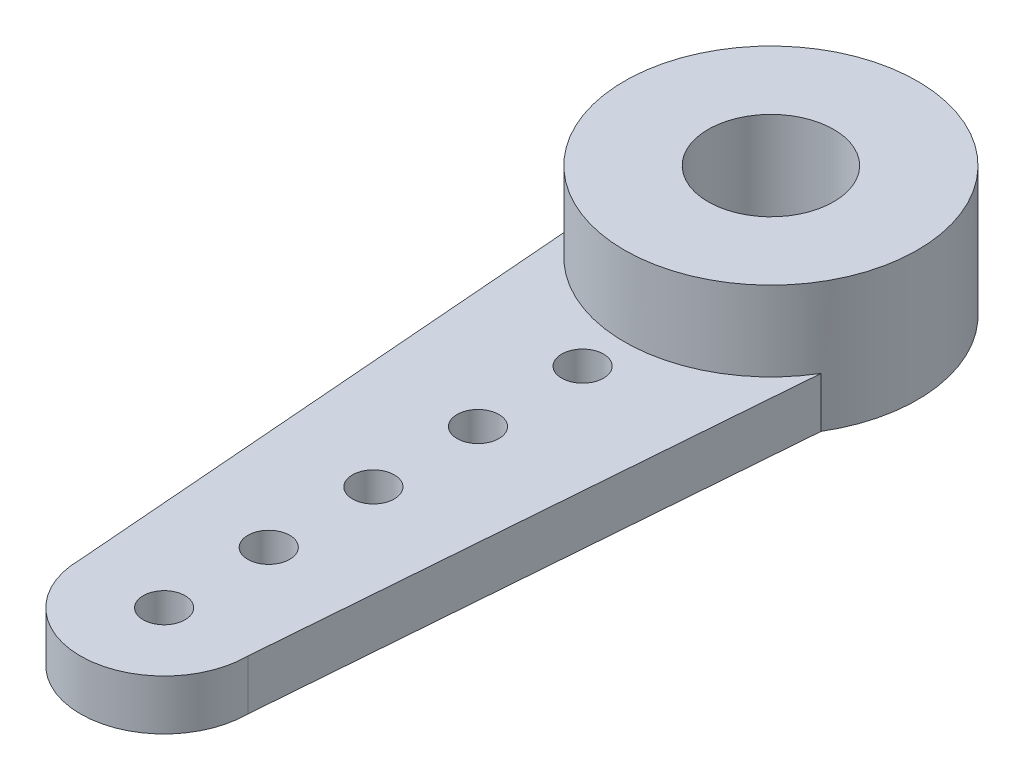
SolidWorks part; units mm, degrees
ref_plane "Front" through (0, 0, 0) normal (0, 0, 1) x (1, 0, 0)
ref_plane "Top" through (0, 0, 0) normal (0, 1, 0) x (1, 0, 0)
ref_plane "Right" through (0, 0, 0) normal (1, 0, 0) x (0, 0, -1)
sketch "草图1" plane through (0, 0, 0) normal (0, 1, 0) x (1, 0, 0)
  line L0 (-81.081, 0) -> (81.6093, 0) construction
  line L1 (0, 48.1996) -> (0, -46.0868) construction
  circle A0 centre (0, 0) radius 3.5
  dimension "D1" = 7
extrude "凸台-拉伸1" add sketch "草图1" along normal blind 3.1
sketch "草图2" plane through (0, 0, 0) normal (0, 1, 0) x (1, 0, 0)
  line L14 (-3, -1.8028) -> (-2, -14.5)
  line L15 (3, -1.8028) -> (2, -14.5)
  arc A1 (2, -14.5) -> (-2, -14.5) centre (0, -14.5) cw
  arc A3 (-3, -1.8028) -> (3, -1.8028) centre (0, 0) ccw
  dimension "D2" = 2
  dimension "D1" = 6
extrude "凸台-拉伸2" add sketch "草图2" along normal blind 1.2
sketch "草图3" plane through (0, 3.1, 0) normal (0, 1, 0) x (1, 0, 0)
  circle A0 centre (0, 0) radius 1.5
  dimension "D1" = 3
extrude "切除-拉伸1" cut sketch "草图3" against normal blind 3
sketch "草图4" plane through (0, 1.2, 0) normal (0, 1, 0) x (1, 0, 0)
  circle A0 centre (0, -14.5) radius 0.5
  circle A1 centre (0, -12) radius 0.5
  circle A2 centre (0, -9.5) radius 0.5
  circle A3 centre (0, -7) radius 0.5
  circle A4 centre (0, -4.5) radius 0.5
  dimension "D1" = 5
extrude "切除-拉伸2" cut sketch "草图4" against normal up to next
ref_axis "基准轴1" through (0, 0.1, 0) along (0, 1, 0)
ref_axis "基准轴2" through (0, 0, 14.5) along (0, 1, 0)
